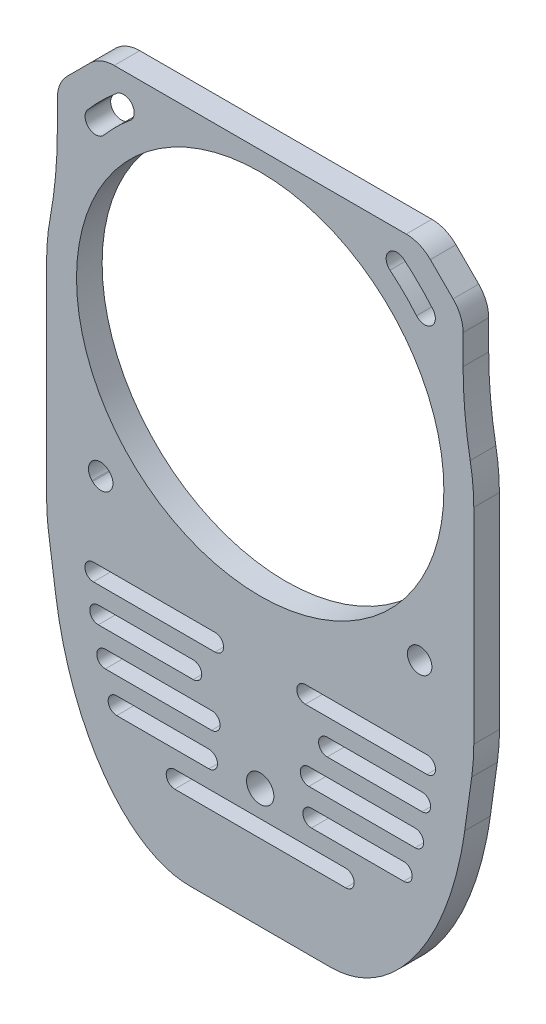
SolidWorks part; units mm, degrees
material "Thornel Mat VMA"
ref_plane "Front Plane" through (0, 0, 0) normal (0, 0, 1) x (1, 0, 0)
ref_plane "Top Plane" through (0, 0, 0) normal (0, 1, 0) x (1, 0, 0)
ref_plane "Right Plane" through (0, 0, 0) normal (1, 0, 0) x (0, 0, -1)
sketch "Sketch1" plane through (0, 0, 0) normal (0, 0, 1) x (1, 0, 0)
  line L5 (5.2845, -23.8125) -> (19.5212, -23.8125)
  line L6 (19.5212, -21.8125) -> (5.2845, -21.8125)
  line L7 (5.2845, -23.8125) -> (19.5212, -23.8125)
  line L8 (19.5212, -21.8125) -> (5.2845, -21.8125)
  line L9 (-5.6903, -29.9375) -> (-18.13, -29.9375)
  line L15 (-18.13, -31.9375) -> (-5.6903, -31.9375)
  line L16 (-5.6903, -29.9375) -> (-18.13, -29.9375)
  line L17 (-18.13, -31.9375) -> (-5.6903, -31.9375)
  line L18 (-6, -34) -> (-16.7931, -34)
  line L19 (-16.7931, -36) -> (-6, -36)
  line L26 (-6, -34) -> (-16.7931, -34)
  line L27 (-16.7931, -36) -> (-6, -36)
  line L30 (-7.8381, -25.875) -> (-18.9502, -25.875)
  line L31 (-18.9502, -27.875) -> (-7.8381, -27.875)
  line L34 (-7.8381, -25.875) -> (-18.9502, -25.875)
  line L35 (-18.9502, -27.875) -> (-7.8381, -27.875)
  line L38 (-5.2845, -21.8125) -> (-19.5212, -21.8125)
  line L39 (-19.5212, -23.8125) -> (-5.2845, -23.8125)
  line L42 (-5.2845, -21.8125) -> (-19.5212, -21.8125)
  line L43 (-19.5212, -23.8125) -> (-5.2845, -23.8125)
  line L46 (7.8381, -27.875) -> (18.9502, -27.875)
  line L47 (18.9502, -25.875) -> (7.8381, -25.875)
  line L50 (7.8381, -27.875) -> (18.9502, -27.875)
  line L51 (18.9502, -25.875) -> (7.8381, -25.875)
  line L54 (6, -36) -> (16.7931, -36)
  line L55 (16.7931, -34) -> (6, -34)
  line L58 (6, -36) -> (16.7931, -36)
  line L62 (16.7931, -34) -> (6, -34)
  line L63 (-10, -40.0625) -> (10, -40.0625)
  line L68 (10, -38.0625) -> (-10, -38.0625)
  line L69 (-10, -40.0625) -> (10, -40.0625)
  line L70 (10, -38.0625) -> (-10, -38.0625)
  line L72 (5.6903, -31.9375) -> (18.13, -31.9375)
  line L74 (18.13, -29.9375) -> (5.6903, -29.9375)
  line L75 (5.6903, -31.9375) -> (18.13, -31.9375)
  line L76 (18.13, -29.9375) -> (5.6903, -29.9375)
  line L77 (12.4122, 10) -> (17.1245, 10)
  line L78 (-17.1245, 10) -> (-12.4122, 10)
  line L79 (12.4122, 10) -> (17.1245, 10)
  line L80 (-17.1245, 10) -> (-12.4122, 10)
  line L81 (17.1245, 2) -> (12.4122, 2)
  line L82 (-12.4122, 2) -> (-17.1245, 2)
  line L83 (17.1245, 2) -> (12.4122, 2)
  line L94 (-12.4122, 2) -> (-17.1245, 2)
  line L103 (-8.2627, -49) -> (8.2627, -49)
  line L104 (23.9369, -27.3245) -> (24.7602, -21.4587)
  line L105 (25, -18.0135) -> (25, 6)
  line L106 (23.75, 19.6359) -> (23.75, 23.0931)
  line L107 (22.5784, 25.9216) -> (19.9216, 28.5784)
  line L108 (17.0931, 29.75) -> (-17.0931, 29.75)
  line L109 (-19.9216, 28.5784) -> (-22.5784, 25.9216)
  line L110 (-23.75, 23.0931) -> (-23.75, 19.6359)
  line L111 (-25, 6) -> (-25, -18.0135)
  line L112 (-24.7602, -21.4587) -> (-23.9369, -27.3245)
  line L113 (-8.2627, -49) -> (8.2627, -49)
  line L114 (23.9369, -27.3245) -> (24.7602, -21.4587)
  line L115 (25, -18.0135) -> (25, 6)
  line L116 (23.75, 19.6359) -> (23.75, 23.0931)
  line L117 (22.5784, 25.9216) -> (19.9216, 28.5784)
  line L118 (17.0931, 29.75) -> (-17.0931, 29.75)
  line L119 (-19.9216, 28.5784) -> (-22.5784, 25.9216)
  line L120 (-23.75, 23.0931) -> (-23.75, 19.6359)
  line L121 (-25, 6) -> (-25, -18.0135)
  line L122 (-24.7602, -21.4587) -> (-23.9369, -27.3245)
  circle A3 centre (0, -35) radius 1.6
  circle A4 centre (0, -35) radius 1.6
  circle A5 centre (-6.2577, 7.7581) radius 1.25
  arc A6 (-15.1966, 25.1465) -> (-16.7926, 27.0708) centre (-15.9946, 26.1087) ccw
  arc A7 (-15.1966, 25.1465) -> (-18.297, 22.081) centre (0.7636, 5.904) ccw
  arc A8 (-20.203, 23.6988) -> (-18.297, 22.081) centre (-19.25, 22.8899) ccw
  arc A9 (-16.7926, 27.0708) -> (-20.203, 23.6988) centre (0.7636, 5.904) ccw
  arc A15 (-15.1966, 25.1465) -> (-16.7926, 27.0708) centre (-15.9946, 26.1087) ccw
  arc A16 (-15.1966, 25.1465) -> (-18.297, 22.081) centre (0.7636, 5.904) ccw
  arc A17 (-20.203, 23.6988) -> (-18.297, 22.081) centre (-19.25, 22.8899) ccw
  arc A22 (-16.7926, 27.0708) -> (-20.203, 23.6988) centre (0.7636, 5.904) ccw
  arc A23 (-19.6918, -13.6232) -> (-19.6232, -13.6918) centre (0, 6) ccw
  arc A24 (-17.7085, -11.6468) -> (-19.6918, -13.6232) centre (-18.7002, -12.635) ccw
  arc A25 (-17.7085, -11.6468) -> (-17.6468, -11.7085) centre (0, 6) ccw
  arc A30 (-19.6232, -13.6918) -> (-17.6468, -11.7085) centre (-18.635, -12.7002) ccw
  arc A31 (-19.6918, -13.6232) -> (-19.6232, -13.6918) centre (0, 6) ccw
  arc A32 (-17.7085, -11.6468) -> (-19.6918, -13.6232) centre (-18.7002, -12.635) ccw
  arc A33 (-17.7085, -11.6468) -> (-17.6468, -11.7085) centre (0, 6) ccw
  arc A38 (-19.6232, -13.6918) -> (-17.6468, -11.7085) centre (-18.635, -12.7002) ccw
  arc A39 (17.6468, -11.7085) -> (19.6232, -13.6918) centre (18.635, -12.7002) ccw
  arc A40 (17.6468, -11.7085) -> (17.7085, -11.6468) centre (0, 6) ccw
  arc A41 (19.6918, -13.6232) -> (17.7085, -11.6468) centre (18.7002, -12.635) ccw
  arc A46 (19.6232, -13.6918) -> (19.6918, -13.6232) centre (0, 6) ccw
  arc A47 (17.6468, -11.7085) -> (19.6232, -13.6918) centre (18.635, -12.7002) ccw
  arc A48 (17.6468, -11.7085) -> (17.7085, -11.6468) centre (0, 6) ccw
  arc A49 (19.6918, -13.6232) -> (17.7085, -11.6468) centre (18.7002, -12.635) ccw
  arc A50 (19.6232, -13.6918) -> (19.6918, -13.6232) centre (0, 6) ccw
  arc A51 (18.297, 22.081) -> (20.203, 23.6988) centre (19.25, 22.8899) ccw
  arc A57 (18.297, 22.081) -> (15.1966, 25.1465) centre (-0.7636, 5.904) ccw
  arc A60 (16.7926, 27.0708) -> (15.1966, 25.1465) centre (15.9946, 26.1087) ccw
  arc A61 (20.203, 23.6988) -> (16.7926, 27.0708) centre (-0.7636, 5.904) ccw
  arc A64 (18.297, 22.081) -> (20.203, 23.6988) centre (19.25, 22.8899) ccw
  arc A65 (18.297, 22.081) -> (15.1966, 25.1465) centre (-0.7636, 5.904) ccw
  arc A68 (16.7926, 27.0708) -> (15.1966, 25.1465) centre (15.9946, 26.1087) ccw
  arc A69 (20.203, 23.6988) -> (16.7926, 27.0708) centre (-0.7636, 5.904) ccw
  arc A72 (19.5212, -23.8125) -> (19.5212, -21.8125) centre (19.5212, -22.8125) ccw
  arc A73 (5.2845, -21.8125) -> (5.2845, -23.8125) centre (5.2845, -22.8125) ccw
  arc A76 (19.5212, -23.8125) -> (19.5212, -21.8125) centre (19.5212, -22.8125) ccw
  arc A77 (5.2845, -21.8125) -> (5.2845, -23.8125) centre (5.2845, -22.8125) ccw
  arc A80 (-18.13, -29.9375) -> (-18.13, -31.9375) centre (-18.13, -30.9375) ccw
  arc A81 (-5.6903, -31.9375) -> (-5.6903, -29.9375) centre (-5.6903, -30.9375) ccw
  arc A84 (-18.13, -29.9375) -> (-18.13, -31.9375) centre (-18.13, -30.9375) ccw
  arc A85 (-5.6903, -31.9375) -> (-5.6903, -29.9375) centre (-5.6903, -30.9375) ccw
  arc A88 (-16.7931, -34) -> (-16.7931, -36) centre (-16.7931, -35) ccw
  arc A89 (-6, -36) -> (-6, -34) centre (-6, -35) ccw
  arc A93 (-16.7931, -34) -> (-16.7931, -36) centre (-16.7931, -35) ccw
  arc A95 (-6, -36) -> (-6, -34) centre (-6, -35) ccw
  arc A100 (-18.9502, -25.875) -> (-18.9502, -27.875) centre (-18.9502, -26.875) ccw
  arc A101 (-7.8381, -27.875) -> (-7.8381, -25.875) centre (-7.8381, -26.875) ccw
  arc A102 (-18.9502, -25.875) -> (-18.9502, -27.875) centre (-18.9502, -26.875) ccw
  arc A104 (-7.8381, -27.875) -> (-7.8381, -25.875) centre (-7.8381, -26.875) ccw
  arc A105 (-19.5212, -21.8125) -> (-19.5212, -23.8125) centre (-19.5212, -22.8125) ccw
  arc A112 (-5.2845, -23.8125) -> (-5.2845, -21.8125) centre (-5.2845, -22.8125) ccw
  arc A113 (-19.5212, -21.8125) -> (-19.5212, -23.8125) centre (-19.5212, -22.8125) ccw
  arc A114 (-5.2845, -23.8125) -> (-5.2845, -21.8125) centre (-5.2845, -22.8125) ccw
  arc A115 (18.9502, -27.875) -> (18.9502, -25.875) centre (18.9502, -26.875) ccw
  arc A116 (7.8381, -25.875) -> (7.8381, -27.875) centre (7.8381, -26.875) ccw
  arc A117 (18.9502, -27.875) -> (18.9502, -25.875) centre (18.9502, -26.875) ccw
  arc A126 (7.8381, -25.875) -> (7.8381, -27.875) centre (7.8381, -26.875) ccw
  arc A127 (16.7931, -36) -> (16.7931, -34) centre (16.7931, -35) ccw
  arc A128 (6, -34) -> (6, -36) centre (6, -35) ccw
  arc A129 (16.7931, -36) -> (16.7931, -34) centre (16.7931, -35) ccw
  arc A130 (6, -34) -> (6, -36) centre (6, -35) ccw
  arc A131 (10, -40.0625) -> (10, -38.0625) centre (10, -39.0625) ccw
  arc A132 (-10, -38.0625) -> (-10, -40.0625) centre (-10, -39.0625) ccw
  arc A133 (10, -40.0625) -> (10, -38.0625) centre (10, -39.0625) ccw
  arc A134 (-10, -38.0625) -> (-10, -40.0625) centre (-10, -39.0625) ccw
  arc A135 (18.13, -31.9375) -> (18.13, -29.9375) centre (18.13, -30.9375) ccw
  arc A144 (5.6903, -29.9375) -> (5.6903, -31.9375) centre (5.6903, -30.9375) ccw
  arc A145 (18.13, -31.9375) -> (18.13, -29.9375) centre (18.13, -30.9375) ccw
  arc A146 (5.6903, -29.9375) -> (5.6903, -31.9375) centre (5.6903, -30.9375) ccw
  circle A147 centre (-6.2577, 7.7581) radius 1.25
  circle A148 centre (6.2577, 4.2419) radius 1.25
  circle A149 centre (6.2577, 4.2419) radius 1.25
  circle A150 centre (0, 6) radius 4
  circle A151 centre (0, 6) radius 4
  arc A155 (19.9015, 14.1351) -> (-19.9015, 14.1351) centre (0, 6) ccw
  arc A156 (17.1245, 10) -> (19.9015, 14.1351) centre (17.1245, 13) ccw
  arc A157 (9.7991, 11.5263) -> (12.4122, 10) centre (12.4122, 13) ccw
  arc A158 (9.7991, 11.5263) -> (-9.7991, 11.5263) centre (0, 6) ccw
  arc A159 (-12.4122, 10) -> (-9.7991, 11.5263) centre (-12.4122, 13) ccw
  arc A160 (-19.9015, 14.1351) -> (-17.1245, 10) centre (-17.1245, 13) ccw
  arc A162 (17.1245, 10) -> (19.9015, 14.1351) centre (17.1245, 13) ccw
  arc A163 (9.7991, 11.5263) -> (12.4122, 10) centre (12.4122, 13) ccw
  arc A164 (9.7991, 11.5263) -> (-9.7991, 11.5263) centre (0, 6) ccw
  arc A165 (-12.4122, 10) -> (-9.7991, 11.5263) centre (-12.4122, 13) ccw
  arc A166 (-19.9015, 14.1351) -> (-17.1245, 10) centre (-17.1245, 13) ccw
  arc A167 (19.9015, -2.1351) -> (17.1245, 2) centre (17.1245, -1) ccw
  arc A168 (-19.9015, -2.1351) -> (19.9015, -2.1351) centre (0, 6) ccw
  arc A169 (-17.1245, 2) -> (-19.9015, -2.1351) centre (-17.1245, -1) ccw
  arc A170 (-9.7991, 0.4737) -> (-12.4122, 2) centre (-12.4122, -1) ccw
  arc A171 (-9.7991, 0.4737) -> (9.7991, 0.4737) centre (0, 6) ccw
  arc A172 (12.4122, 2) -> (9.7991, 0.4737) centre (12.4122, -1) ccw
  arc A173 (19.9015, -2.1351) -> (17.1245, 2) centre (17.1245, -1) ccw
  arc A175 (-17.1245, 2) -> (-19.9015, -2.1351) centre (-17.1245, -1) ccw
  arc A176 (-9.7991, 0.4737) -> (-12.4122, 2) centre (-12.4122, -1) ccw
  arc A177 (-9.7991, 0.4737) -> (9.7991, 0.4737) centre (0, 6) ccw
  arc A178 (12.4122, 2) -> (9.7991, 0.4737) centre (12.4122, -1) ccw
  arc A183 (25, 6) -> (24.5833, 10.5453) centre (0, 6) ccw
  arc A184 (23.75, 19.6359) -> (24.5833, 10.5453) centre (73.75, 19.6359) ccw
  arc A185 (23.75, 23.0931) -> (22.5784, 25.9216) centre (19.75, 23.0931) ccw
  arc A186 (19.9216, 28.5784) -> (17.0931, 29.75) centre (17.0931, 25.75) ccw
  arc A187 (-17.0931, 29.75) -> (-19.9216, 28.5784) centre (-17.0931, 25.75) ccw
  arc A188 (-22.5784, 25.9216) -> (-23.75, 23.0931) centre (-19.75, 23.0931) ccw
  arc A189 (-24.5833, 10.5453) -> (-23.75, 19.6359) centre (-73.75, 19.6359) ccw
  arc A190 (-24.5833, 10.5453) -> (-25, 6) centre (0, 6) ccw
  arc A191 (25, 6) -> (24.5833, 10.5453) centre (0, 6) ccw
  arc A192 (23.75, 19.6359) -> (24.5833, 10.5453) centre (73.75, 19.6359) ccw
  arc A193 (23.75, 23.0931) -> (22.5784, 25.9216) centre (19.75, 23.0931) ccw
  arc A194 (19.9216, 28.5784) -> (17.0931, 29.75) centre (17.0931, 25.75) ccw
  arc A195 (-17.0931, 29.75) -> (-19.9216, 28.5784) centre (-17.0931, 25.75) ccw
  arc A196 (-22.5784, 25.9216) -> (-23.75, 23.0931) centre (-19.75, 23.0931) ccw
  arc A197 (-24.5833, 10.5453) -> (-23.75, 19.6359) centre (-73.75, 19.6359) ccw
  arc A198 (-24.5833, 10.5453) -> (-25, 6) centre (0, 6) ccw
  arc A235 (19.9015, 14.1351) -> (-19.9015, 14.1351) centre (0, 6) ccw
  arc A236 (-19.9015, -2.1351) -> (19.9015, -2.1351) centre (0, 6) ccw
  ellipse E4 centre (9.3222, -22.8431) end of major axis (7.7445, -48.9844) minor radius 15 (8.2627, -49) -> (23.9369, -27.3245) ccw
  ellipse E5 centre (10, -18.0135) end of major axis (10, -37.3575) minor radius 15 (24.7602, -21.4587) -> (25, -18.0135) ccw
  ellipse E6 centre (-10, -18.0135) end of major axis (-10, -37.3575) minor radius 15 (-25, -18.0135) -> (-24.7602, -21.4587) ccw
  ellipse E7 centre (-9.3222, -22.8431) end of major axis (-10.8998, 3.2982) minor radius 15 (-23.9369, -27.3245) -> (-8.2627, -49) ccw
  ellipse E8 centre (9.3222, -22.8431) end of major axis (7.7445, -48.9844) minor radius 15 (8.2627, -49) -> (23.9369, -27.3245) ccw
  ellipse E9 centre (10, -18.0135) end of major axis (10, -37.3575) minor radius 15 (24.7602, -21.4587) -> (25, -18.0135) ccw
  ellipse E10 centre (-10, -18.0135) end of major axis (-10, -37.3575) minor radius 15 (-25, -18.0135) -> (-24.7602, -21.4587) ccw
  ellipse E11 centre (-9.3222, -22.8431) end of major axis (-7.7445, -48.9844) minor radius 15 (-23.9369, -27.3245) -> (-8.2627, -49) ccw
  dimension "D1" = 0
  dimension "D2" = 0
  dimension "D3" = 0
  dimension "D4" = 0
  dimension "D5" = 0
  dimension "D6" = 0
  dimension "D7" = 0
  dimension "D8" = 0
  dimension "D9" = 0
  dimension "D10" = 0
  dimension "D11" = 0
  dimension "D12" = 0
  dimension "D13" = 0
  dimension "D14" = 0
  dimension "D15" = 0
  dimension "D16" = 0
  dimension "D17" = 0
  dimension "D18" = 0
  dimension "D19" = 0
  dimension "D20" = 0
extrude "Boss-Extrude1" add sketch "Sketch1" along normal blind 3 contours L122 E11 L113 E8 L114 E9 L115 A191 A192 L116 A193 L117 A194 L118 A195 L119 A196 L120 A197 A198 L121 E10 A4 A22 A15 A16 A17 A38 A31 A32 A33 A50 A47 A48 A49 A69 A64 A65 A68 A77 L8 A76 L7 A85 region at (-18.6368, -40.4536, 0)
sketch "Sketch2" plane through (0, 0, 3) normal (0, 0, 1) x (1, 0, 0)
  circle A0 centre (0, 6) radius 21.5
  arc A2 (19.9015, 14.1351) -> (-19.9015, 14.1351) centre (0, 6) ccw construction
extrude "Cut-Extrude1" cut sketch "Sketch2" against normal through all
